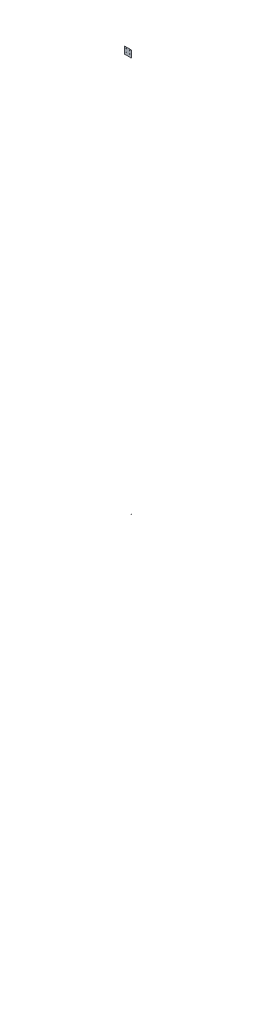
SolidWorks part; units mm, degrees
ref_plane "Piano frontale" through (0, 0, 0) normal (0, 0, 1) x (1, 0, 0)
ref_plane "Piano superiore" through (0, 0, 0) normal (0, 1, 0) x (1, 0, 0)
ref_plane "Piano destro" through (0, 0, 0) normal (1, 0, 0) x (0, 0, -1)
sketch "Schizzo1" plane through (0, 0, 0) normal (0, 0, 1) x (1, 0, 0)
  line L0 (10, 448) -> (10, -28.2593) construction
  line L1 (0, 0) -> (448, 0)
  line L2 (0, 0) -> (0, 448)
  line L3 (0, 448) -> (448, 448)
  line L4 (448, 0) -> (448, 448)
  line L5 (0, 224) -> (448, 224) construction
  line L6 (224, 448) -> (224, 0) construction
  line L7 (438, 448) -> (438, -28.2593) construction
  line L8 (0, 438) -> (525.0128, 438) construction
  line L9 (0, 10) -> (525.0128, 10) construction
  line L10 (0, 448) -> (0, 224) construction
  line L11 (0, 448) -> (0, 224) construction
  line L12 (9, 336) -> (11, 336) construction
  line L13 (9, 338) -> (11, 338)
  line L14 (9, 334) -> (11, 334)
  line L15 (0, 336) -> (224, 336) construction
  line L16 (9, 112) -> (11, 112) construction
  line L17 (9, 110) -> (11, 110)
  line L18 (9, 114) -> (11, 114)
  line L19 (439, 112) -> (437, 112) construction
  line L20 (439, 110) -> (437, 110)
  line L21 (439, 114) -> (437, 114)
  line L22 (439, 336) -> (437, 336) construction
  line L23 (439, 338) -> (437, 338)
  line L24 (439, 334) -> (437, 334)
  line L25 (112, 448) -> (112, 224) construction
  line L26 (112, 439) -> (112, 437) construction
  line L27 (114, 439) -> (114, 437)
  line L28 (110, 439) -> (110, 437)
  line L29 (336, 439) -> (336, 437) construction
  line L30 (334, 439) -> (334, 437)
  line L31 (338, 439) -> (338, 437)
  line L32 (112, 9) -> (112, 11) construction
  line L33 (114, 9) -> (114, 11)
  line L34 (110, 9) -> (110, 11)
  line L35 (336, 9) -> (336, 11) construction
  line L36 (334, 9) -> (334, 11)
  line L37 (338, 9) -> (338, 11)
  line L38 (36.9588, 287.1268) -> (36.9588, 448) construction
  line L39 (36.9588, 265.3661) -> (36.9588, 309.3661) construction
  line L40 (34.9588, 265.3661) -> (34.9588, 309.3661)
  line L41 (38.9588, 265.3661) -> (38.9588, 309.3661)
  line L42 (36.9588, 182.6339) -> (36.9588, 138.6339) construction
  line L43 (34.9588, 182.6339) -> (34.9588, 138.6339)
  line L44 (38.9588, 182.6339) -> (38.9588, 138.6339)
  line L45 (37.087, 204.1388) -> (37.087, 244.1388) construction
  line L46 (35.087, 204.1388) -> (35.087, 244.1388)
  line L47 (39.087, 204.1388) -> (39.087, 244.1388)
  line L48 (187.0412, 265.3661) -> (187.0412, 309.3661) construction
  line L49 (189.0412, 265.3661) -> (189.0412, 309.3661)
  line L50 (185.0412, 265.3661) -> (185.0412, 309.3661)
  line L51 (186.913, 204.1388) -> (186.913, 244.1388) construction
  line L52 (188.913, 204.1388) -> (188.913, 244.1388)
  line L53 (184.913, 204.1388) -> (184.913, 244.1388)
  line L54 (187.0412, 182.6339) -> (187.0412, 138.6339) construction
  line L55 (189.0412, 182.6339) -> (189.0412, 138.6339)
  line L56 (185.0412, 182.6339) -> (185.0412, 138.6339)
  line L57 (243.9707, 416) -> (263.9707, 416) construction
  line L58 (243.9707, 418) -> (263.9707, 418)
  line L59 (243.9707, 414) -> (263.9707, 414)
  line L60 (243.9707, -12408.6738) -> (263.9707, -12408.6738) construction
  line L61 (243.9707, -12406.6738) -> (263.9707, -12406.6738)
  line L62 (243.9707, -12410.6738) -> (263.9707, -12410.6738)
  line L63 (224, 224) -> (448, 0) construction
  line L64 (448, 224) -> (224, 0) construction
  line L65 (224, 224) -> (448, 224) construction
  line L66 (336, 112) -> (335.9892, 224.0001) construction
  line L67 (336, 112) -> (448, 112) construction
  line L68 (243.9707, -25233.3476) -> (263.9707, -25233.3476) construction
  line L69 (243.9707, -25231.3476) -> (263.9707, -25231.3476)
  line L70 (243.9707, -25235.3476) -> (263.9707, -25235.3476)
  line L71 (243.9707, -38058.0214) -> (263.9707, -38058.0214) construction
  line L72 (243.9707, -38056.0214) -> (263.9707, -38056.0214)
  line L73 (243.9707, -38060.0214) -> (263.9707, -38060.0214)
  line L83 (427.9707, 416.0177) -> (407.9707, 416.0139) construction
  line L84 (427.9703, 418.0177) -> (407.9703, 418.0139)
  line L85 (427.9711, 414.0177) -> (407.9711, 414.0139)
  line L89 (243.9707, 384) -> (263.9707, 384) construction
  line L90 (243.9707, 386) -> (263.9707, 386)
  line L91 (243.9707, 382) -> (263.9707, 382)
  line L92 (427.9707, 384.0177) -> (407.9707, 384.0139) construction
  line L93 (427.9703, 386.0177) -> (407.9703, 386.0139)
  line L94 (427.9711, 382.0177) -> (407.9711, 382.0139)
  line L95 (279.9725, 383.005) -> (279.9725, 412.995) construction
  line L96 (277.8725, 383.005) -> (277.8725, 412.995)
  line L97 (282.0725, 383.005) -> (282.0725, 412.995)
  line L98 (243.9707, 352) -> (263.9707, 352) construction
  line L99 (243.9707, 354) -> (263.9707, 354)
  line L100 (243.9707, 350) -> (263.9707, 350)
  line L101 (427.9707, 352.0177) -> (407.9707, 352.0139) construction
  line L102 (427.9703, 354.0177) -> (407.9703, 354.0139)
  line L103 (427.9711, 350.0177) -> (407.9711, 350.0139)
  line L104 (243.9707, 320) -> (263.9707, 320) construction
  line L105 (243.9707, 322) -> (263.9707, 322)
  line L106 (243.9707, 318) -> (263.9707, 318)
  line L107 (427.9707, 320.0177) -> (407.9707, 320.0139) construction
  line L108 (427.9703, 322.0177) -> (407.9703, 322.0139)
  line L109 (427.9711, 318.0177) -> (407.9711, 318.0139)
  line L110 (243.9707, 288) -> (263.9707, 288) construction
  line L111 (391.9724, 383.0058) -> (391.9724, 413.0158) construction
  line L112 (394.0724, 383.0058) -> (394.0724, 413.0158)
  line L113 (389.8724, 383.0058) -> (389.8724, 413.0158)
  line L114 (336, 112) -> (202.345, 112) construction
  line L115 (243.9707, -50882.6953) -> (263.9707, -50882.6953) construction
  line L116 (243.9707, -50880.6953) -> (263.9707, -50880.6953)
  line L117 (243.9707, -50884.6953) -> (263.9707, -50884.6953)
  line L118 (243.9707, 290) -> (263.9707, 290)
  line L119 (437.8536, -50882.6766) -> (417.8536, -50882.6804) construction
  line L120 (437.8532, -50880.6766) -> (417.8532, -50880.6804)
  line L121 (437.854, -50884.6766) -> (417.854, -50884.6804)
  line L122 (243.9707, 286) -> (263.9707, 286)
  line L123 (435.3829, -38058.003) -> (415.3829, -38058.0069) construction
  line L124 (435.3825, -38056.003) -> (415.3825, -38056.0069)
  line L125 (435.3833, -38060.003) -> (415.3833, -38060.0069)
  line L126 (432.9122, -25233.3294) -> (412.9122, -25233.3333) construction
  line L127 (432.9118, -25231.3294) -> (412.9118, -25231.3333)
  line L128 (432.9125, -25235.3294) -> (412.9125, -25235.3333)
  line L129 (430.4414, -12408.6559) -> (410.4414, -12408.6597) construction
  line L130 (430.4411, -12406.6559) -> (410.4411, -12406.6597)
  line L131 (430.4418, -12410.6559) -> (410.4418, -12410.6597)
  line L132 (427.9707, 288.0177) -> (407.9707, 288.0139) construction
  line L133 (427.9703, 290.0177) -> (407.9703, 290.0139)
  line L134 (427.9711, 286.0177) -> (407.9711, 286.0139)
  line L135 (243.9707, 256) -> (263.9707, 256) construction
  line L136 (243.9707, 258) -> (263.9707, 258)
  line L137 (243.9707, 254) -> (263.9707, 254)
  line L138 (427.9707, 256.0177) -> (407.9707, 256.0139) construction
  line L139 (427.9703, 258.0177) -> (407.9703, 258.0139)
  line L140 (427.9711, 254.0177) -> (407.9711, 254.0139)
  line L141 (243.9707, 224) -> (263.9707, 224) construction
  line L142 (243.9707, 226) -> (263.9707, 226)
  line L143 (243.9707, 222) -> (263.9707, 222)
  line L144 (427.9707, 224.0177) -> (407.9707, 224.0139) construction
  line L145 (427.9703, 226.0177) -> (407.9703, 226.0139)
  line L146 (427.9711, 222.0177) -> (407.9711, 222.0139)
  line L147 (243.9707, 192) -> (263.9707, 192) construction
  line L148 (243.9707, 194) -> (263.9707, 194)
  line L149 (243.9707, 190) -> (263.9707, 190)
  line L150 (427.9707, 192.0177) -> (407.9707, 192.0139) construction
  line L151 (427.9703, 194.0177) -> (407.9703, 194.0139)
  line L152 (427.9711, 190.0177) -> (407.9711, 190.0139)
  line L153 (243.9707, 160) -> (263.9707, 160) construction
  line L154 (243.9707, 162) -> (263.9707, 162)
  line L155 (243.9707, 158) -> (263.9707, 158)
  line L156 (427.9707, 160.0177) -> (407.9707, 160.0139) construction
  line L157 (427.9703, 162.0177) -> (407.9703, 162.0139)
  line L158 (427.9711, 158.0177) -> (407.9711, 158.0139)
  line L159 (243.9707, 128) -> (263.9707, 128) construction
  line L160 (243.9707, 130) -> (263.9707, 130)
  line L161 (243.9707, 126) -> (263.9707, 126)
  line L162 (427.9707, 128.0177) -> (407.9707, 128.0139) construction
  line L163 (427.9703, 130.0177) -> (407.9703, 130.0139)
  line L164 (427.9711, 126.0177) -> (407.9711, 126.0139)
  line L165 (279.9725, 333.005) -> (279.9725, 362.995) construction
  line L166 (277.8725, 333.005) -> (277.8725, 362.995)
  line L167 (282.0725, 333.005) -> (282.0725, 362.995)
  line L168 (391.9724, 333.0058) -> (391.9724, 363.0158) construction
  line L169 (394.0724, 333.0058) -> (394.0724, 363.0158)
  line L170 (389.8724, 333.0058) -> (389.8724, 363.0158)
  line L171 (279.9725, 283.005) -> (279.9725, 312.995) construction
  line L172 (277.8725, 283.005) -> (277.8725, 312.995)
  line L173 (282.0725, 283.005) -> (282.0725, 312.995)
  line L174 (391.9724, 283.0058) -> (391.9724, 313.0158) construction
  line L175 (394.0724, 283.0058) -> (394.0724, 313.0158)
  line L176 (389.8724, 283.0058) -> (389.8724, 313.0158)
  line L177 (279.9725, 233.005) -> (279.9725, 262.995) construction
  line L178 (277.8725, 233.005) -> (277.8725, 262.995)
  line L179 (282.0725, 233.005) -> (282.0725, 262.995)
  line L180 (391.9724, 233.0058) -> (391.9724, 263.0158) construction
  line L181 (394.0724, 233.0058) -> (394.0724, 263.0158)
  line L182 (389.8724, 233.0058) -> (389.8724, 263.0158)
  line L183 (279.9725, 183.005) -> (279.9725, 212.995) construction
  line L184 (277.8725, 183.005) -> (277.8725, 212.995)
  line L185 (282.0725, 183.005) -> (282.0725, 212.995)
  line L186 (391.9724, 183.0058) -> (391.9724, 213.0158) construction
  line L187 (394.0724, 183.0058) -> (394.0724, 213.0158)
  line L188 (389.8724, 183.0058) -> (389.8724, 213.0158)
  line L189 (279.9725, 133.005) -> (279.9725, 162.995) construction
  line L190 (277.8725, 133.005) -> (277.8725, 162.995)
  line L191 (282.0725, 133.005) -> (282.0725, 162.995)
  line L192 (391.9724, 133.0058) -> (391.9724, 163.0158) construction
  line L193 (394.0724, 133.0058) -> (394.0724, 163.0158)
  line L194 (389.8724, 133.0058) -> (389.8724, 163.0158)
  line L195 (279.9725, 83.005) -> (279.9725, 112.995) construction
  line L196 (277.8725, 83.005) -> (277.8725, 112.995)
  line L197 (282.0725, 83.005) -> (282.0725, 112.995)
  line L198 (391.9724, 83.0058) -> (391.9724, 113.0158) construction
  line L199 (394.0724, 83.0058) -> (394.0724, 113.0158)
  line L200 (389.8724, 83.0058) -> (389.8724, 113.0158)
  line L201 (243.9707, 96) -> (263.9707, 96) construction
  line L202 (243.9707, 98) -> (263.9707, 98)
  line L203 (243.9707, 94) -> (263.9707, 94)
  line L204 (427.9707, 96.0177) -> (407.9707, 96.0139) construction
  line L205 (427.9703, 98.0177) -> (407.9703, 98.0139)
  line L206 (427.9711, 94.0177) -> (407.9711, 94.0139)
  line L207 (243.9707, 64) -> (263.9707, 64) construction
  line L208 (243.9707, 66) -> (263.9707, 66)
  line L209 (243.9707, 62) -> (263.9707, 62)
  line L210 (427.9707, 64.0177) -> (407.9707, 64.0139) construction
  line L211 (427.9703, 66.0177) -> (407.9703, 66.0139)
  line L212 (427.9711, 62.0177) -> (407.9711, 62.0139)
  line L213 (243.9707, 32) -> (263.9707, 32) construction
  line L214 (243.9707, 34) -> (263.9707, 34)
  line L215 (243.9707, 30) -> (263.9707, 30)
  line L216 (427.9707, 32.0177) -> (407.9707, 32.0139) construction
  line L217 (427.9703, 34.0177) -> (407.9703, 34.0139)
  line L218 (427.9711, 30.0177) -> (407.9711, 30.0139)
  arc A0 (9, 338) -> (9, 334) centre (9, 336) ccw
  arc A1 (11, 334) -> (11, 338) centre (11, 336) ccw
  arc A2 (9, 110) -> (9, 114) centre (9, 112) cw
  arc A3 (11, 114) -> (11, 110) centre (11, 112) cw
  arc A4 (439, 110) -> (439, 114) centre (439, 112) ccw
  arc A5 (437, 114) -> (437, 110) centre (437, 112) ccw
  arc A6 (439, 338) -> (439, 334) centre (439, 336) cw
  arc A7 (437, 334) -> (437, 338) centre (437, 336) cw
  arc A8 (114, 439) -> (110, 439) centre (112, 439) ccw
  arc A9 (110, 437) -> (114, 437) centre (112, 437) ccw
  arc A10 (334, 439) -> (338, 439) centre (336, 439) cw
  arc A11 (338, 437) -> (334, 437) centre (336, 437) cw
  arc A12 (114, 9) -> (110, 9) centre (112, 9) cw
  arc A13 (110, 11) -> (114, 11) centre (112, 11) cw
  arc A14 (334, 9) -> (338, 9) centre (336, 9) ccw
  arc A15 (338, 11) -> (334, 11) centre (336, 11) ccw
  arc A16 (34.9588, 265.3661) -> (38.9588, 265.3661) centre (36.9588, 265.3661) ccw
  arc A17 (38.9588, 309.3661) -> (34.9588, 309.3661) centre (36.9588, 309.3661) ccw
  arc A18 (34.9588, 182.6339) -> (38.9588, 182.6339) centre (36.9588, 182.6339) cw
  arc A19 (38.9588, 138.6339) -> (34.9588, 138.6339) centre (36.9588, 138.6339) cw
  arc A20 (35.087, 204.1388) -> (39.087, 204.1388) centre (37.087, 204.1388) ccw
  arc A21 (39.087, 244.1388) -> (35.087, 244.1388) centre (37.087, 244.1388) ccw
  arc A22 (189.0412, 265.3661) -> (185.0412, 265.3661) centre (187.0412, 265.3661) cw
  arc A23 (185.0412, 309.3661) -> (189.0412, 309.3661) centre (187.0412, 309.3661) cw
  arc A24 (188.913, 204.1388) -> (184.913, 204.1388) centre (186.913, 204.1388) cw
  arc A25 (184.913, 244.1388) -> (188.913, 244.1388) centre (186.913, 244.1388) cw
  arc A26 (189.0412, 182.6339) -> (185.0412, 182.6339) centre (187.0412, 182.6339) ccw
  arc A27 (185.0412, 138.6339) -> (189.0412, 138.6339) centre (187.0412, 138.6339) ccw
  arc A28 (243.9707, 418) -> (243.9707, 414) centre (243.9707, 416) ccw
  arc A29 (263.9707, 414) -> (263.9707, 418) centre (263.9707, 416) ccw
  arc A30 (243.9707, -12406.6738) -> (243.9707, -12410.6738) centre (243.9707, -12408.6738) ccw
  arc A31 (263.9707, -12410.6738) -> (263.9707, -12406.6738) centre (263.9707, -12408.6738) ccw
  arc A32 (243.9707, -25231.3476) -> (243.9707, -25235.3476) centre (243.9707, -25233.3476) ccw
  arc A33 (263.9707, -25235.3476) -> (263.9707, -25231.3476) centre (263.9707, -25233.3476) ccw
  arc A34 (243.9707, -38056.0214) -> (243.9707, -38060.0214) centre (243.9707, -38058.0214) ccw
  arc A35 (263.9707, -38060.0214) -> (263.9707, -38056.0214) centre (263.9707, -38058.0214) ccw
  arc A36 (427.9703, 418.0177) -> (427.9711, 414.0177) centre (427.9707, 416.0177) cw
  arc A37 (407.9711, 414.0139) -> (407.9703, 418.0139) centre (407.9707, 416.0139) cw
  arc A38 (243.9707, 386) -> (243.9707, 382) centre (243.9707, 384) ccw
  arc A39 (263.9707, 382) -> (263.9707, 386) centre (263.9707, 384) ccw
  arc A40 (427.9703, 386.0177) -> (427.9711, 382.0177) centre (427.9707, 384.0177) cw
  arc A41 (407.9711, 382.0139) -> (407.9703, 386.0139) centre (407.9707, 384.0139) cw
  arc A42 (243.9707, 354) -> (243.9707, 350) centre (243.9707, 352) ccw
  arc A43 (263.9707, 350) -> (263.9707, 354) centre (263.9707, 352) ccw
  arc A44 (427.9703, 354.0177) -> (427.9711, 350.0177) centre (427.9707, 352.0177) cw
  arc A45 (407.9711, 350.0139) -> (407.9703, 354.0139) centre (407.9707, 352.0139) cw
  circle A48 centre (335.9707, 416) radius 4
  circle A49 centre (335.9707, 384) radius 4
  arc A52 (243.9707, 322) -> (243.9707, 318) centre (243.9707, 320) ccw
  arc A53 (263.9707, 318) -> (263.9707, 322) centre (263.9707, 320) ccw
  arc A56 (427.9703, 322.0177) -> (427.9711, 318.0177) centre (427.9707, 320.0177) cw
  arc A57 (407.9711, 318.0139) -> (407.9703, 322.0139) centre (407.9707, 320.0139) cw
  arc A58 (243.9707, 290) -> (243.9707, 286) centre (243.9707, 288) ccw
  arc A59 (263.9707, 286) -> (263.9707, 290) centre (263.9707, 288) ccw
  arc A60 (277.8725, 383.005) -> (282.0725, 383.005) centre (279.9725, 383.005) ccw
  arc A61 (282.0725, 412.995) -> (277.8725, 412.995) centre (279.9725, 412.995) ccw
  arc A62 (427.9703, 290.0177) -> (427.9711, 286.0177) centre (427.9707, 288.0177) cw
  arc A63 (407.9711, 286.0139) -> (407.9703, 290.0139) centre (407.9707, 288.0139) cw
  arc A64 (243.9707, 258) -> (243.9707, 254) centre (243.9707, 256) ccw
  arc A65 (263.9707, 254) -> (263.9707, 258) centre (263.9707, 256) ccw
  arc A66 (427.9703, 258.0177) -> (427.9711, 254.0177) centre (427.9707, 256.0177) cw
  arc A67 (407.9711, 254.0139) -> (407.9703, 258.0139) centre (407.9707, 256.0139) cw
  arc A68 (243.9707, 226) -> (243.9707, 222) centre (243.9707, 224) ccw
  arc A69 (263.9707, 222) -> (263.9707, 226) centre (263.9707, 224) ccw
  arc A70 (394.0724, 383.0058) -> (389.8724, 383.0058) centre (391.9724, 383.0058) cw
  arc A71 (389.8724, 413.0158) -> (394.0724, 413.0158) centre (391.9724, 413.0158) cw
  arc A72 (243.9707, -50880.6953) -> (243.9707, -50884.6953) centre (243.9707, -50882.6953) ccw
  arc A73 (263.9707, -50884.6953) -> (263.9707, -50880.6953) centre (263.9707, -50882.6953) ccw
  arc A74 (437.8532, -50880.6766) -> (437.854, -50884.6766) centre (437.8536, -50882.6766) cw
  arc A75 (417.854, -50884.6804) -> (417.8532, -50880.6804) centre (417.8536, -50882.6804) cw
  arc A76 (435.3825, -38056.003) -> (435.3833, -38060.003) centre (435.3829, -38058.003) cw
  arc A77 (415.3833, -38060.0069) -> (415.3825, -38056.0069) centre (415.3829, -38058.0069) cw
  arc A78 (432.9118, -25231.3294) -> (432.9125, -25235.3294) centre (432.9122, -25233.3294) cw
  arc A79 (412.9125, -25235.3333) -> (412.9118, -25231.3333) centre (412.9122, -25233.3333) cw
  arc A80 (430.4411, -12406.6559) -> (430.4418, -12410.6559) centre (430.4414, -12408.6559) cw
  arc A81 (410.4418, -12410.6597) -> (410.4411, -12406.6597) centre (410.4414, -12408.6597) cw
  arc A82 (427.9703, 226.0177) -> (427.9711, 222.0177) centre (427.9707, 224.0177) cw
  arc A83 (407.9711, 222.0139) -> (407.9703, 226.0139) centre (407.9707, 224.0139) cw
  arc A84 (243.9707, 194) -> (243.9707, 190) centre (243.9707, 192) ccw
  arc A85 (263.9707, 190) -> (263.9707, 194) centre (263.9707, 192) ccw
  arc A86 (427.9703, 194.0177) -> (427.9711, 190.0177) centre (427.9707, 192.0177) cw
  arc A87 (407.9711, 190.0139) -> (407.9703, 194.0139) centre (407.9707, 192.0139) cw
  arc A88 (243.9707, 162) -> (243.9707, 158) centre (243.9707, 160) ccw
  arc A89 (263.9707, 158) -> (263.9707, 162) centre (263.9707, 160) ccw
  arc A90 (427.9703, 162.0177) -> (427.9711, 158.0177) centre (427.9707, 160.0177) cw
  arc A91 (407.9711, 158.0139) -> (407.9703, 162.0139) centre (407.9707, 160.0139) cw
  arc A92 (243.9707, 130) -> (243.9707, 126) centre (243.9707, 128) ccw
  arc A93 (263.9707, 126) -> (263.9707, 130) centre (263.9707, 128) ccw
  arc A94 (427.9703, 130.0177) -> (427.9711, 126.0177) centre (427.9707, 128.0177) cw
  arc A95 (407.9711, 126.0139) -> (407.9703, 130.0139) centre (407.9707, 128.0139) cw
  arc A96 (277.8725, 333.005) -> (282.0725, 333.005) centre (279.9725, 333.005) ccw
  arc A97 (282.0725, 362.995) -> (277.8725, 362.995) centre (279.9725, 362.995) ccw
  arc A98 (394.0724, 333.0058) -> (389.8724, 333.0058) centre (391.9724, 333.0058) cw
  arc A99 (389.8724, 363.0158) -> (394.0724, 363.0158) centre (391.9724, 363.0158) cw
  arc A100 (277.8725, 283.005) -> (282.0725, 283.005) centre (279.9725, 283.005) ccw
  arc A101 (282.0725, 312.995) -> (277.8725, 312.995) centre (279.9725, 312.995) ccw
  arc A102 (394.0724, 283.0058) -> (389.8724, 283.0058) centre (391.9724, 283.0058) cw
  arc A103 (389.8724, 313.0158) -> (394.0724, 313.0158) centre (391.9724, 313.0158) cw
  arc A104 (277.8725, 233.005) -> (282.0725, 233.005) centre (279.9725, 233.005) ccw
  arc A105 (282.0725, 262.995) -> (277.8725, 262.995) centre (279.9725, 262.995) ccw
  arc A106 (394.0724, 233.0058) -> (389.8724, 233.0058) centre (391.9724, 233.0058) cw
  arc A107 (389.8724, 263.0158) -> (394.0724, 263.0158) centre (391.9724, 263.0158) cw
  arc A108 (277.8725, 183.005) -> (282.0725, 183.005) centre (279.9725, 183.005) ccw
  arc A109 (282.0725, 212.995) -> (277.8725, 212.995) centre (279.9725, 212.995) ccw
  arc A110 (394.0724, 183.0058) -> (389.8724, 183.0058) centre (391.9724, 183.0058) cw
  arc A111 (389.8724, 213.0158) -> (394.0724, 213.0158) centre (391.9724, 213.0158) cw
  arc A112 (277.8725, 133.005) -> (282.0725, 133.005) centre (279.9725, 133.005) ccw
  arc A113 (282.0725, 162.995) -> (277.8725, 162.995) centre (279.9725, 162.995) ccw
  arc A114 (394.0724, 133.0058) -> (389.8724, 133.0058) centre (391.9724, 133.0058) cw
  arc A115 (389.8724, 163.0158) -> (394.0724, 163.0158) centre (391.9724, 163.0158) cw
  arc A116 (277.8725, 83.005) -> (282.0725, 83.005) centre (279.9725, 83.005) ccw
  arc A117 (282.0725, 112.995) -> (277.8725, 112.995) centre (279.9725, 112.995) ccw
  arc A118 (394.0724, 83.0058) -> (389.8724, 83.0058) centre (391.9724, 83.0058) cw
  arc A119 (389.8724, 113.0158) -> (394.0724, 113.0158) centre (391.9724, 113.0158) cw
  arc A120 (243.9707, 98) -> (243.9707, 94) centre (243.9707, 96) ccw
  arc A121 (263.9707, 94) -> (263.9707, 98) centre (263.9707, 96) ccw
  arc A122 (427.9703, 98.0177) -> (427.9711, 94.0177) centre (427.9707, 96.0177) cw
  arc A123 (407.9711, 94.0139) -> (407.9703, 98.0139) centre (407.9707, 96.0139) cw
  arc A124 (243.9707, 66) -> (243.9707, 62) centre (243.9707, 64) ccw
  arc A125 (263.9707, 62) -> (263.9707, 66) centre (263.9707, 64) ccw
  arc A126 (427.9703, 66.0177) -> (427.9711, 62.0177) centre (427.9707, 64.0177) cw
  arc A127 (407.9711, 62.0139) -> (407.9703, 66.0139) centre (407.9707, 64.0139) cw
  arc A128 (243.9707, 34) -> (243.9707, 30) centre (243.9707, 32) ccw
  arc A129 (263.9707, 30) -> (263.9707, 34) centre (263.9707, 32) ccw
  arc A130 (427.9703, 34.0177) -> (427.9711, 30.0177) centre (427.9707, 32.0177) cw
  arc A131 (407.9711, 30.0139) -> (407.9703, 34.0139) centre (407.9707, 32.0139) cw
  circle A132 centre (335.9707, 352) radius 4
  circle A133 centre (335.9707, 320) radius 4
  circle A134 centre (335.9707, 288) radius 4
  circle A135 centre (335.9707, 256) radius 4
  circle A136 centre (335.9707, 224) radius 4
  circle A137 centre (335.9707, 192) radius 4
  circle A138 centre (335.9707, 160) radius 4
  circle A139 centre (335.9707, 128) radius 4
  circle A140 centre (335.9707, 96) radius 4
  circle A141 centre (335.9707, 64) radius 4
  circle A142 centre (335.9707, 32) radius 4
  circle A143 centre (112.0293, 32) radius 4
  circle A144 centre (112.0293, 64) radius 4
  circle A145 centre (112.0293, 96) radius 4
  circle A146 centre (112.0293, 128) radius 4
  circle A147 centre (112.0293, 160) radius 4
  circle A148 centre (112.0293, 192) radius 4
  circle A149 centre (112.0293, 224) radius 4
  circle A150 centre (112.0293, 256) radius 4
  circle A151 centre (112.0293, 288) radius 4
  circle A152 centre (112.0293, 320) radius 4
  circle A153 centre (112.0293, 352) radius 4
  circle A154 centre (112.0293, 384) radius 4
  circle A155 centre (112.0293, 416) radius 4
  point P19 (10, 336)
  point P28 (10, 112)
  point P35 (438, 112)
  point P42 (438, 336)
  point P49 (112, 438)
  point P52 (112, 438)
  point P59 (336, 438)
  point P66 (112, 10)
  point P73 (336, 10)
  point P82 (36.9588, 287.3661)
  point P89 (36.9588, 160.6339)
  point P96 (37.087, 224.1388)
  point P103 (187.0412, 287.3661)
  point P110 (186.913, 224.1388)
  point P117 (187.0412, 160.6339)
  point P124 (253.9707, 416)
  point P132 (253.9707, -12408.6738)
  point P143 (253.9707, -25233.3476)
  point P150 (253.9707, -38058.0214)
  point P155 (417.9707, 416.0158)
  point P164 (253.9707, 384)
  point P171 (417.9707, 384.0158)
  point P179 (280.1758, 232.4048)
  point P193 (280.1085, 282.4047)
  point P197 (253.9707, 352)
  point P207 (280.0413, 332.4047)
  point P214 (417.9707, 352.0158)
  point P221 (253.9707, 320)
  point P227 (279.9725, 398)
  point P235 (417.9707, 320.0158)
  point P242 (253.9707, 288)
  point P249 (417.9707, 288.0158)
  point P256 (253.9707, 256)
  point P262 (391.9724, 398.0108)
  point P271 (253.9707, -50882.6953)
  point P279 (427.8536, -50882.6785)
  point P288 (425.3829, -38058.0049)
  point P295 (422.9122, -25233.3314)
  point P302 (420.4414, -12408.6578)
  point P307 (417.9707, 256.0158)
  point P314 (253.9707, 224)
  point P321 (417.9707, 224.0158)
  point P328 (253.9707, 192)
  point P335 (417.9707, 192.0158)
  point P342 (253.9707, 160)
  point P349 (417.9707, 160.0158)
  point P356 (253.9707, 128)
  point P363 (417.9707, 128.0158)
  point P370 (279.9725, 348)
  point P377 (391.9724, 348.0108)
  point P384 (279.9725, 298)
  point P391 (391.9724, 298.0108)
  point P398 (279.9725, 248)
  point P405 (391.9724, 248.0108)
  point P412 (279.9725, 198)
  point P419 (391.9724, 198.0108)
  point P426 (279.9725, 148)
  point P433 (391.9724, 148.0108)
  point P440 (279.9725, 98)
  point P447 (391.9724, 98.0108)
  point P454 (253.9707, 96)
  point P461 (417.9707, 96.0158)
  point P468 (253.9707, 64)
  point P475 (417.9707, 64.0158)
  point P482 (253.9707, 32)
  point P489 (417.9707, 32.0158)
  dimension "D5" = 1
  dimension "D14" = 82
  dimension "D23" = 5
  dimension "D21" = 7
  dimension "D18" = 8
  dimension "D1" = 448
  dimension "D2" = 448
  dimension "D3" = 10
  dimension "D4" = 10
  dimension "D6" = 4
  dimension "D7" = 112
  dimension "D8" = 112
  dimension "D9" = 1
  dimension "D10" = 4
  dimension "D11" = 4
  dimension "D12" = 22
  dimension "D13" = 4
  dimension "D15" = 32
  dimension "D16" = 20
  dimension "D17" = 50
  dimension "D19" = 20
  dimension "D20" = 13
  dimension "D25" = 112
extrude "Estrusione-Estrusione1" add sketch "Schizzo1" against normal blind 3
